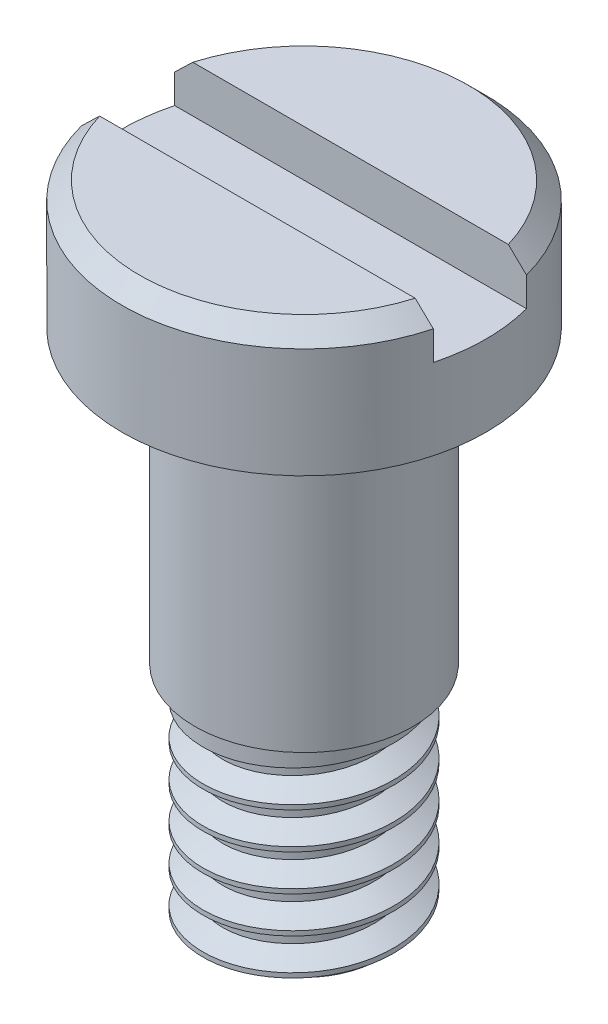
SolidWorks part; units mm, degrees
ref_plane "Front Plane" through (0, 0, 0) normal (0, 0, 1) x (1, 0, 0)
ref_plane "Top Plane" through (0, 0, 0) normal (0, 1, 0) x (1, 0, 0)
ref_plane "Right Plane" through (0, 0, 0) normal (1, 0, 0) x (0, 0, -1)
sketch "Sketch1" plane through (0, 0, 0) normal (0, 1, 0) x (1, 0, 0)
  circle A0 centre (0, 0) radius 2.3812
  dimension "D1" = 4.7625
extrude "Boss-Extrude1" add sketch "Sketch1" along normal blind 6.35
sketch "Sketch2" plane through (0, 6.35, 0) normal (0, 1, 0) x (1, 0, 0)
  circle A0 centre (0, 0) radius 3.9688
  dimension "D1" = 7.9375
extrude "Boss-Extrude2" add sketch "Sketch2" along normal blind 2.7781
chamfer "Chamfer1" distance 0.381 angle 45 1 edges at (0, 9.1281, 3.9688)
sketch "Sketch3" plane through (0, 0, 0) normal (0, -1, 0) x (1, 0, 0)
  circle A0 centre (0, 0) radius 2.0828
  dimension "D1" = 4.1656
extrude "Boss-Extrude3" add sketch "Sketch3" along normal blind 4.7625
thread "Thread1" pitch 0.7937 method cut profile "Thread Profile1" start angle 0, offset 0, length 0, pitch 0.7937, diameter 4.1656
ref_plane "Plane1" through (-2.0828, 0, 0) normal (0, 0, 1) x (-1, 0, 0)
sketch "Thread Profile1" plane through (-2.0828, 0, 0) normal (0, 0, 1) x (-1, 0, 0)
  line L0 (0, 0) -> (0, 0.7937) construction
  line L11 (0, 0) -> (0, 0.6945)
  line L12 (0, 0.6945) -> (-0.4296, 0.4465)
  line L13 (-0.4296, 0.4465) -> (-0.4296, 0.248)
  line L15 (-0.4296, 0.248) -> (0, 0)
  line L17 (-0.4296, 0.3473) -> (0, 0.3473) construction
  point P2 (0, 0)
  dimension "Pitch" = 0.7937
  dimension "Profile_Angle" = 60
  dimension "Profile_Land" = 0.1984
  dimension "Profile_Height" = 0.4296
sketch "Sketch7" plane through (0, 9.1281, 0) normal (0, 1, 0) x (1, 0, 0)
  line L1 (-4.5452, 1.016) -> (4.8108, 1.016)
  line L2 (-4.5452, 1.016) -> (-4.5452, -1.016)
  line L3 (-4.5452, -1.016) -> (4.8108, -1.016)
  line L4 (4.8108, 1.016) -> (4.8108, -1.016)
  dimension "D1" = 2.032
  dimension "D2" = 1.016
extrude "Cut-Extrude1" cut sketch "Sketch7" against normal blind 1.016
